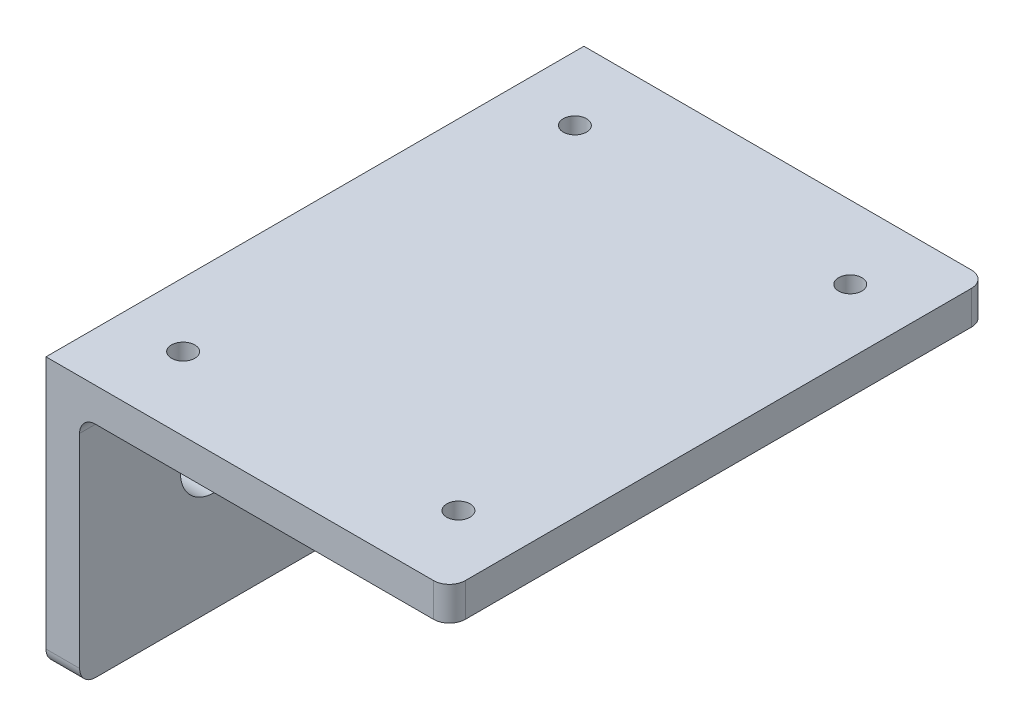
SolidWorks part; units mm, degrees
material "ABS"
ref_plane "Front Plane" through (0, 0, 0) normal (0, 0, 1) x (1, 0, 0)
ref_plane "Top Plane" through (0, 0, 0) normal (0, 1, 0) x (1, 0, 0)
ref_plane "Right Plane" through (0, 0, 0) normal (1, 0, 0) x (0, 0, -1)
sketch "Sketch2" plane through (0, 0, 0) normal (1, 0, 0) x (0, 0, -1)
  line L1 (-25.4, -12.7) -> (25.4, -12.7)
  line L2 (-25.4, -12.7) -> (-25.4, 12.7)
  line L3 (-25.4, 12.7) -> (25.4, 12.7)
  line L4 (25.4, -12.7) -> (25.4, 12.7)
  line L5 (-25.4, -12.7) -> (25.4, 12.7) construction
  line L6 (-25.4, 12.7) -> (25.4, -12.7) construction
  point P0 (0, 0)
  dimension "D1" = 25.4
  dimension "D2" = 50.8
extrude "Boss-Extrude1" add sketch "Sketch2" along normal blind 3.175
sketch "Sketch4" plane through (0, 12.7, 0) normal (0, 1, 0) x (1, 0, 0)
  line L1 (0, 25.4) -> (38.1, 25.4)
  line L2 (0, 25.4) -> (0, -25.4)
  line L3 (0, -25.4) -> (38.1, -25.4)
  line L4 (38.1, 25.4) -> (38.1, -25.4)
  dimension "D1" = 50.8
  dimension "D2" = 38.1
extrude "Boss-Extrude2" add sketch "Sketch4" against normal blind 3.175
sketch "Sketch5" plane through (0, 12.7, 0) normal (0, 1, 0) x (1, 0, 0)
  line L1 (6.05, -18.5) -> (32.05, -18.5) construction
  line L2 (6.05, -18.5) -> (6.05, 18.5) construction
  line L3 (6.05, 18.5) -> (32.05, 18.5) construction
  line L4 (32.05, -18.5) -> (32.05, 18.5) construction
  line L5 (6.05, -18.5) -> (32.05, 18.5) construction
  line L6 (6.05, 18.5) -> (32.05, -18.5) construction
  circle A0 centre (6.05, 18.5) radius 1.1
  circle A1 centre (32.05, 18.5) radius 1.1
  circle A2 centre (32.05, -18.5) radius 1.1
  circle A3 centre (6.05, -18.5) radius 1.1
  point P0 (19.05, 0)
  dimension "D1" = 26
  dimension "D2" = 37
extrude "Cut-Extrude1" cut sketch "Sketch5" against normal blind 3.175
sketch "Sketch6" plane through (0, 0, 0) normal (-1, 0, 0) x (0, 0, 1)
  line L0 (12.7, 0) -> (-12.7, 0) construction
  circle A0 centre (-12.7, 0) radius 3.175
  circle A1 centre (12.7, 0) radius 3.175
  point P4 (0, 0)
extrude "Cut-Extrude2" cut sketch "Sketch6" against normal blind 3.175
sketch "Sketch7" plane through (0, 0, 0) normal (0, 0, 1) x (1, 0, 0)
  line L2 (3.175, -12.7) -> (25.4, 9.525)
  line L3 (3.175, 9.525) -> (38.1, 9.525) construction
  line L8 (3.175, -12.7) -> (3.175, 9.525)
  line L9 (25.4, 9.525) -> (3.175, 9.525)
extrude "Boss-Extrude3" add sketch "Sketch7" along normal mid plane 3.175
fillet "Fillet3" radius 1.5 11 edges at (3.175, -1.5875, -1.5875) (14.2875, 9.525, -1.5875) (25.4, 9.525, 0) (3.175, -1.5875, 1.5875) (14.2875, 9.525, 1.5875) (3.175, 9.525, 13.4937) (3.175, 9.525, -13.4937) (1.5875, -12.7, 25.4) (1.5875, -12.7, -25.4) (38.1, 11.1125, 25.4) (38.1, 11.1125, -25.4)
